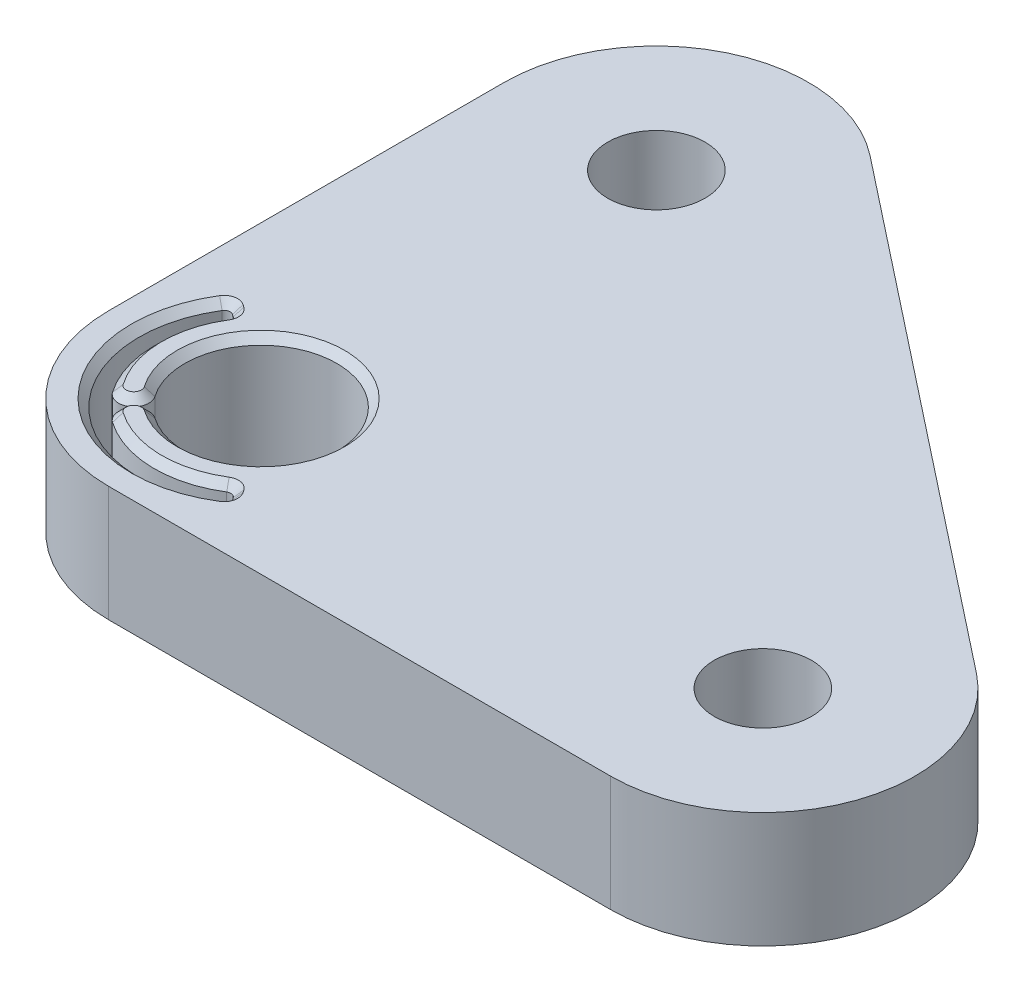
SolidWorks part; units mm, degrees
ref_plane "Front" through (0, 0, 0) normal (0, 0, 1) x (1, 0, 0)
ref_plane "Top" through (0, 0, 0) normal (0, 1, 0) x (1, 0, 0)
ref_plane "Right" through (0, 0, 0) normal (1, 0, 0) x (0, 0, -1)
sketch "Sketch1" plane through (0, 0, 0) normal (0, 1, 0) x (1, 0, 0)
  line L0 (0, 0) -> (16.5, 0) construction
  line L1 (16.5, 0) -> (0, 13) construction
  line L2 (0, 13) -> (0, 0) construction
  line L3 (-5, -5) -> (30.9254, -5)
  line L4 (30.9254, -5) -> (-5, 23.3048)
  line L5 (-5, 23.3048) -> (-5, -5)
  circle A0 centre (16.5, 0) radius 1.6
  circle A1 centre (0, 0) radius 2.5
  circle A2 centre (0, 13) radius 1.6
  dimension "D3" = 5
  dimension "D4" = 3.2
  dimension "D1" = 16.5
  dimension "D2" = 13
  dimension "D5" = 5
extrude "Boss-Extrude1" add sketch "Sketch1" along normal blind 1.57
fillet "Fillet1" radius 5 3 edges at (-5, 0.785, -23.3048) (-5, 0.785, 5) (30.9254, 0.785, 5)
other "Move Face1" [suppressed] offset 0.0762 parameters "D1"=0.0762
sketch "Sketch2" plane through (0, 1.57, 0) normal (0, 1, 0) x (1, 0, 0)
  line L3 (19.5944, 3.9275) -> (3.0944, 16.9275)
  line L4 (-5, 13) -> (-5, 0)
  line L5 (0, -5) -> (16.5, -5)
  line L6 (19.5944, 3.9275) -> (3.0944, 16.9275)
  line L7 (-5, 13) -> (-5, 0)
  line L8 (0, -5) -> (16.5, -5)
  circle A0 centre (0, 0) radius 2.5 construction
  circle A1 centre (16.5, 0) radius 1.6 construction
  circle A2 centre (0, 13) radius 1.6 construction
  arc A3 (3.0944, 16.9275) -> (-5, 13) centre (0, 13) ccw
  arc A4 (-5, 0) -> (0, -5) centre (0, 0) ccw
  arc A5 (16.5, -5) -> (19.5944, 3.9275) centre (16.5, 0) ccw
  arc A6 (3.0944, 16.9275) -> (-5, 13) centre (0, 13) ccw
  arc A7 (-5, 0) -> (0, -5) centre (0, 0) ccw
  arc A8 (16.5, -5) -> (19.5944, 3.9275) centre (16.5, 0) ccw
  circle A9 centre (0, 0) radius 2.5
  circle A10 centre (16.5, 0) radius 1.6
  circle A11 centre (0, 13) radius 1.6
  dimension "D1" = 0
extrude "Boss-Extrude2" add sketch "Sketch2" along normal blind 2.23
sketch "Sketch3" plane through (0, 0, 0) normal (0, -1, 0) x (1, 0, 0)
  circle A0 centre (16.5, 0) radius 3
  circle A1 centre (0, -13) radius 3
  circle A2 centre (0, -13) radius 1.6 construction
  circle A3 centre (16.5, 0) radius 1.6 construction
  circle A4 centre (0, -13) radius 1.6
  circle A5 centre (16.5, 0) radius 1.6
  dimension "D1" = 6
extrude "Boss-Extrude3" add sketch "Sketch3" along normal blind 1
sketch "Sketch4" plane through (0, 3.8, 0) normal (0, 1, 0) x (1, 0, 0)
  line B0 (1.7207, -2.4575) -> (0, 0) construction
  line B1 (2.1191, -3.0264) -> (2.1766, -3.1085)
  line B2 (-3.0264, 2.1191) -> (-3.1085, 2.1766)
  line B3 (-1.7207, -2.4575) -> (0, 0) construction
  arc B4 (2.1187, -3.3928) -> (-3.3928, 2.1187) centre (0, 0) cw
  arc B5 (-1.4339, -2.0479) -> (-2.0075, -2.867) centre (-1.7207, -2.4575) ccw
  arc B6 (-2.0075, -2.867) -> (1.8496, -2.9714) centre (0, 0) ccw
  arc B7 (-2.867, -2.0075) -> (-2.9714, 1.8496) centre (0, 0) cw
  arc B8 (-2.0479, -1.4339) -> (-2.867, -2.0075) centre (-2.4575, -1.7207) cw
  arc B9 (-1.4339, -2.0479) -> (-2.0479, -1.4339) centre (0, 0) cw
  arc B10 (2.1191, -3.0264) -> (1.8496, -2.9714) centre (1.9553, -3.1411) ccw
  arc B11 (2.1766, -3.1085) -> (2.1187, -3.3928) centre (2.0127, -3.2232) cw
  arc B12 (-3.1085, 2.1766) -> (-3.3928, 2.1187) centre (-3.2232, 2.0127) ccw
  arc B13 (-3.0264, 2.1191) -> (-2.9714, 1.8496) centre (-3.1411, 1.9553) cw
sketch_block_instance "5mm_bore_flexure_relief-1"
sketch_block "5mm_bore_flexure_relief" parameters "D4"=2.5, "D6"=0.2, "D1"=80, "D2"=0.5, "D3"=70, "D5"=1
extrude "Cut-Extrude1" cut sketch "Sketch4" against normal blind 10
sketch "Sketch5" plane through (9.4139, 0, -11.9484) normal (0.6189, 0, -0.7855) x (-0.7855, 0, -0.6189)
  line L0 (-12.9606, 0.2) -> (8.0453, 0.2) construction
  line L1 (-12.9606, 3.8) -> (-12.9606, 0) construction
  line L2 (8.0453, 0) -> (8.0453, 3.8) construction
  line L3 (-12.9606, 0) -> (8.0453, 0) construction
  text T0 "LCR-03" font "Century Gothic" height in points 12
  dimension "D1" = 0.2
extrude "Part Num Left" cut sketch "Sketch5" against normal blind 0.4
chamfer "Chamfer1" distance 1 angle 45 2 edges at (0, 0, -10) (16.5, 0, 3)
chamfer "Chamfer2" distance 0.25 angle 45 12 edges at (-2.8284, 3.8, 2.8284) (2.2087, 3.8, 3.2631) (-3.2631, 3.8, -2.2087) (2.1478, 3.8, 3.0674) (-3.0674, 3.8, -2.1478) (1.9953, 3.8, 2.9452) (-2.9452, 3.8, -1.9953) (-0.0946, 3.8, 3.4987) (-3.4987, 3.8, 0.0946) (-2.1303, 3.8, 2.1707) (-2.1707, 3.8, 2.1303) (1.7678, 3.8, -1.7678)
mirror "Mirror1" [suppressed] of bodies 106 104
delete or keep bodies "Body-Delete/Keep 1" [suppressed] type keep bodies bodies 105
sketch "Sketch6" [suppressed] plane through (-13.2439, 0, -16.8096) normal (-0.6189, 0, -0.7855) x (-0.7855, 0, 0.6189)
  line L0 (-0.1904, 0.2) -> (20.8155, 0.2) construction
  line L1 (-0.1904, 0) -> (-0.1904, 3.8) construction
  line L2 (20.8155, 3.8) -> (20.8155, 0) construction
  line L3 (20.8155, 0) -> (-0.1904, 0) construction
  text T0 "RCR-03" font "Century Gothic" height in points 12
  dimension "D1" = 0.2
extrude "Part Num Right" [suppressed] cut sketch "Sketch6" against normal blind 0.4
